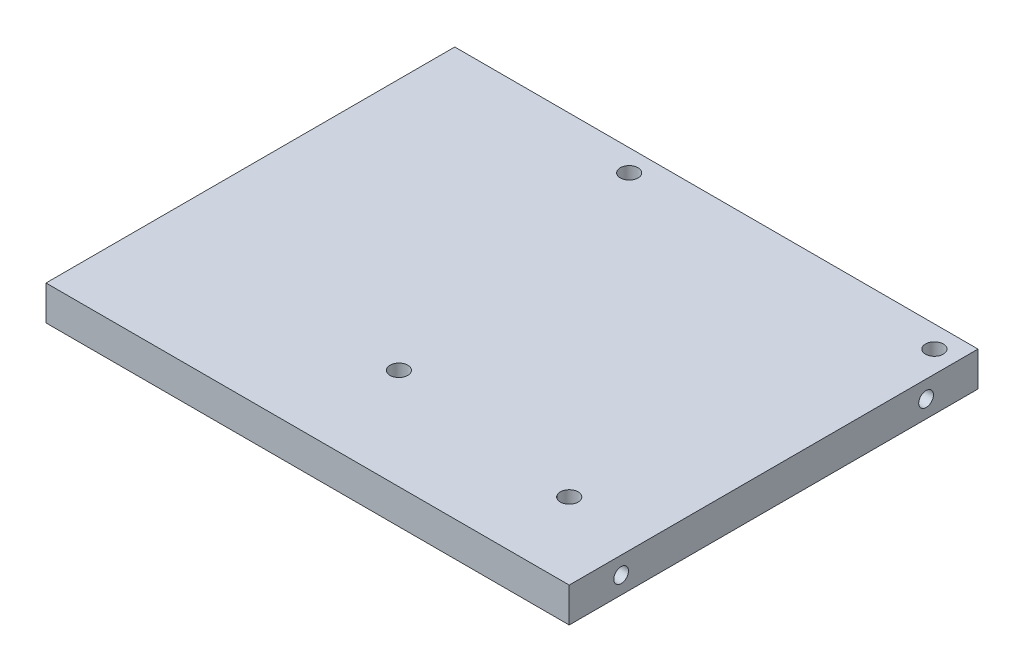
SolidWorks part; units mm, degrees
ref_plane "Front Plane" through (0, 0, 0) normal (0, 0, 1) x (1, 0, 0)
ref_plane "Top Plane" through (0, 0, 0) normal (0, 1, 0) x (1, 0, 0)
ref_plane "Right Plane" through (0, 0, 0) normal (1, 0, 0) x (0, 0, -1)
ref_plane "Plane1" through (0, -8, 0) normal (0, -1, 0) x (-1, 0, 0)
sketch "Sketch1" plane through (0, -8, 0) normal (0, -1, 0) x (-1, 0, 0)
  line L0 (0, 75) -> (0, 0) construction
  line L1 (0, 0) -> (-96, 0)
  line L2 (0, 0) -> (0, 75)
  line L3 (0, 75) -> (-96, 75)
  line L4 (-96, 0) -> (-96, 75)
  line L5 (6.35, 75) -> (0, 75) construction
extrude "Boss-Extrude1" add sketch "Sketch1" against normal blind 6.35
sketch "Sketch2" plane through (0, -8, 0) normal (0, -1, 0) x (1, 0, 0)
  circle A0 centre (36, -71) radius 1.6319
  circle A1 centre (46.25, -18.5) radius 1.6319
  circle A2 centre (82, -14) radius 1.632
  circle A3 centre (92, -71) radius 1.6319
extrude "Cut-Extrude1" cut sketch "Sketch2" against normal blind 6.35
sketch "Sketch3" plane through (0, 0, 0) normal (-1, 0, 0) x (0, 0, 1)
  circle A0 centre (-65.475, -4.825) radius 1.3525
  circle A1 centre (-9.525, -4.825) radius 1.3526
  circle A2 centre (-9.525, -4.825) radius 1.8986 construction
  circle A3 centre (-65.475, -4.825) radius 1.8987 construction
extrude "Cut-Extrude2" cut sketch "Sketch3" against normal blind 9.525
sketch "Sketch4" plane through (96, 0, 0) normal (1, 0, 0) x (0, 0, -1)
  circle A0 centre (65.475, -4.825) radius 1.3525
  circle A1 centre (9.525, -4.825) radius 1.3526
  circle A2 centre (65.475, -4.825) radius 1.8987 construction
  circle A3 centre (9.525, -4.825) radius 1.8987 construction
extrude "Cut-Extrude3" cut sketch "Sketch4" against normal blind 9.525
